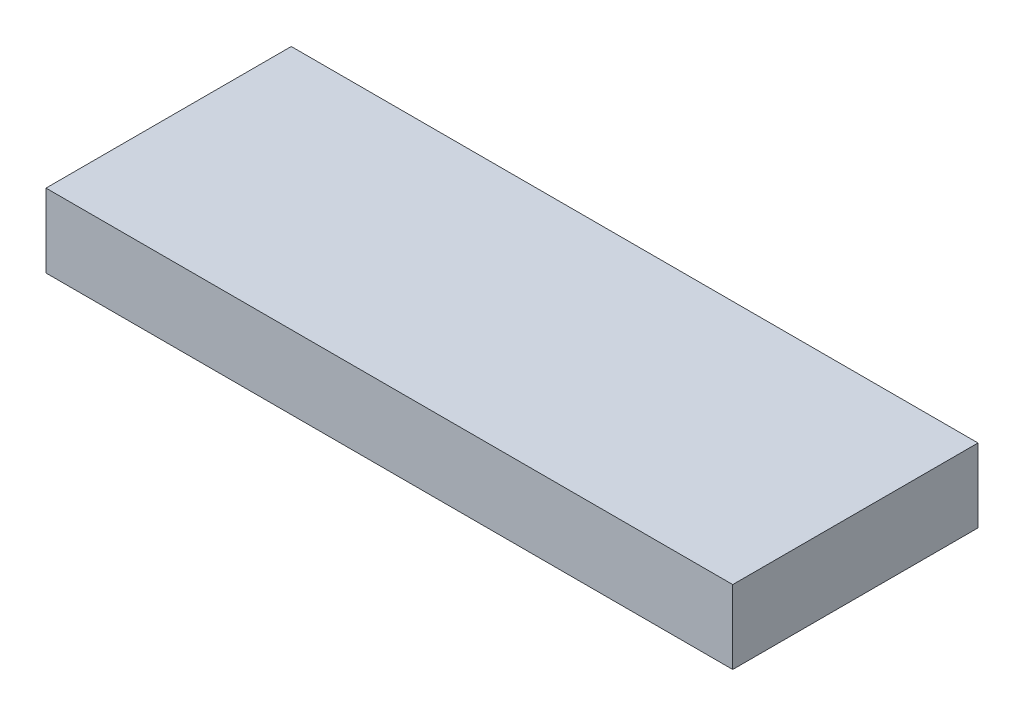
SolidWorks part; units mm, degrees
ref_plane "Front Plane" through (0, 0, 0) normal (0, 0, 1) x (1, 0, 0)
ref_plane "Top Plane" through (0, 0, 0) normal (0, 1, 0) x (1, 0, 0)
ref_plane "Right Plane" through (0, 0, 0) normal (1, 0, 0) x (0, 0, -1)
sketch "Sketch1" plane through (0, 0, 0) normal (1, 0, 0) x (0, 0, -1)
  line L1 (-31.75, -9.525) -> (31.75, -9.525)
  line L2 (-31.75, -9.525) -> (-31.75, 9.525)
  line L3 (-31.75, 9.525) -> (31.75, 9.525)
  line L4 (31.75, -9.525) -> (31.75, 9.525)
  line L5 (-31.75, -9.525) -> (31.75, 9.525) construction
  line L6 (-31.75, 9.525) -> (31.75, -9.525) construction
  point P0 (0, 0)
  dimension "D1" = 63.5
  dimension "D2" = 19.05
extrude "Boss-Extrude1" add sketch "Sketch1" along normal mid plane 177.8
sketch "Sketch2" [suppressed] plane through (0, 0, 0) normal (1, 0, 0) x (0, 0, -1)
  line L0 (-9.525, 9.525) -> (9.525, -9.525)
  line L1 (31.75, 9.525) -> (-31.75, 9.525) construction
  line L2 (-31.75, -9.525) -> (31.75, -9.525) construction
  dimension "D1" = 45
extrude "Cut-Extrude1" [suppressed] cut sketch "Sketch2" against normal through all and the other way through all flip side to cut
sketch "Sketch3" [suppressed] plane through (0, 9.525, 0) normal (0, 1, 0) x (1, 0, 0)
  line L0 (279.4, 0) -> (260.35, 0) construction
  line L1 (-260.35, 10.3187) -> (-171.45, 10.3188)
  line L2 (-260.35, 10.3187) -> (-260.35, -10.3187)
  line L3 (-260.35, -10.3187) -> (-171.45, -10.3188)
  line L4 (-171.45, 10.3188) -> (-171.45, -10.3188)
  line L5 (-152.4, 10.3188) -> (-63.5, 10.3188)
  line L6 (-152.4, 10.3188) -> (-152.4, -10.3188)
  line L7 (-152.4, -10.3188) -> (-63.5, -10.3188)
  line L8 (-63.5, 10.3188) -> (-63.5, -10.3188)
  line L9 (-44.45, 10.3188) -> (44.45, 10.3188)
  line L10 (-44.45, 10.3188) -> (-44.45, -10.3188)
  line L11 (-44.45, -10.3188) -> (44.45, -10.3188)
  line L12 (44.45, 10.3188) -> (44.45, -10.3188)
  line L13 (63.5, 10.3188) -> (152.4, 10.3188)
  line L14 (63.5, 10.3188) -> (63.5, -10.3188)
  line L15 (63.5, -10.3188) -> (152.4, -10.3188)
  line L16 (152.4, 10.3188) -> (152.4, -10.3188)
  line L17 (171.45, 10.3188) -> (260.35, 10.3187)
  line L18 (171.45, 10.3188) -> (171.45, -10.3188)
  line L19 (171.45, -10.3188) -> (260.35, -10.3187)
  line L20 (260.35, 10.3187) -> (260.35, -10.3187)
  line L21 (279.4, 29.3688) -> (279.4, -29.3687) construction
  line L22 (260.35, 0) -> (171.45, 0) construction
  line L23 (171.45, 0) -> (152.4, 0) construction
  line L24 (152.4, 0) -> (63.5, 0) construction
  line L25 (63.5, 0) -> (44.45, 0) construction
  line L26 (44.45, 0) -> (-44.45, 0) construction
  line L27 (-44.45, 0) -> (-63.5, 0) construction
  line L28 (-63.5, 0) -> (-152.4, 0) construction
  line L29 (-152.4, 0) -> (-171.45, 0) construction
  line L30 (-171.45, 0) -> (-260.35, 0) construction
  line L31 (-260.35, 0) -> (-279.4, 0) construction
  line L32 (-279.4, 29.3688) -> (-279.4, -29.3687) construction
  line L33 (215.9, 10.3188) -> (215.9, 29.3688) construction
  line L34 (279.4, 29.3688) -> (-279.4, 29.3688) construction
  dimension "D1" = 19.05
extrude "Cut-Extrude2" [suppressed] cut sketch "Sketch3" against normal through all
sketch "Sketch4" [suppressed] plane through (0, 9.525, 0) normal (0, 1, 0) x (1, 0, 0)
  line L0 (107.95, 0) -> (88.9, 0) construction
  line L1 (-88.9, 12.7) -> (-9.525, 12.7)
  line L2 (-88.9, 12.7) -> (-88.9, -12.7)
  line L3 (-88.9, -12.7) -> (-9.525, -12.7)
  line L4 (-9.525, 12.7) -> (-9.525, -12.7)
  line L5 (88.9, 12.7) -> (9.525, 12.7)
  line L6 (88.9, 12.7) -> (88.9, -12.7)
  line L7 (88.9, -12.7) -> (9.525, -12.7)
  line L8 (9.525, 12.7) -> (9.525, -12.7)
  line L9 (107.95, 31.75) -> (107.95, -31.75) construction
  line L10 (88.9, 0) -> (9.525, 0) construction
  line L11 (9.525, 0) -> (-9.525, 0) construction
  line L12 (-9.525, 0) -> (-88.9, 0) construction
  line L13 (-88.9, 0) -> (-107.95, 0) construction
  line L14 (-107.95, 31.75) -> (-107.95, -31.75) construction
  line L16 (-49.2125, 12.7) -> (-49.2125, 31.75) construction
  line L17 (107.95, 31.75) -> (-107.95, 31.75) construction
  dimension "D1" = 19.05
extrude "Cut-Extrude3" [suppressed] cut sketch "Sketch4" against normal through all
sketch "Sketch5" [suppressed] plane through (0, 9.525, 0) normal (0, 1, 0) x (1, 0, 0)
  line L0 (-88.9, 0) -> (-69.85, 0) construction
  line L1 (-69.85, 12.7) -> (-9.525, 12.7)
  line L2 (-69.85, 12.7) -> (-69.85, -12.7)
  line L3 (-69.85, -12.7) -> (-9.525, -12.7)
  line L4 (-9.525, 12.7) -> (-9.525, -12.7)
  line L5 (9.525, 12.7) -> (69.85, 12.7)
  line L6 (9.525, 12.7) -> (9.525, -12.7)
  line L7 (9.525, -12.7) -> (69.85, -12.7)
  line L8 (69.85, 12.7) -> (69.85, -12.7)
  line L9 (-88.9, 31.75) -> (-88.9, -31.75) construction
  line L10 (-69.85, 0) -> (-9.525, 0) construction
  line L11 (-9.525, 0) -> (9.525, 0) construction
  line L12 (9.525, 0) -> (69.85, 0) construction
  line L13 (69.85, 0) -> (88.9, 0) construction
  line L14 (88.9, 31.75) -> (88.9, -31.75) construction
  line L16 (39.6875, 12.7) -> (39.6875, 31.75) construction
  line L17 (88.9, 31.75) -> (-88.9, 31.75) construction
  dimension "D1" = 19.05
extrude "Cut-Extrude4" [suppressed] cut sketch "Sketch5" against normal through all
